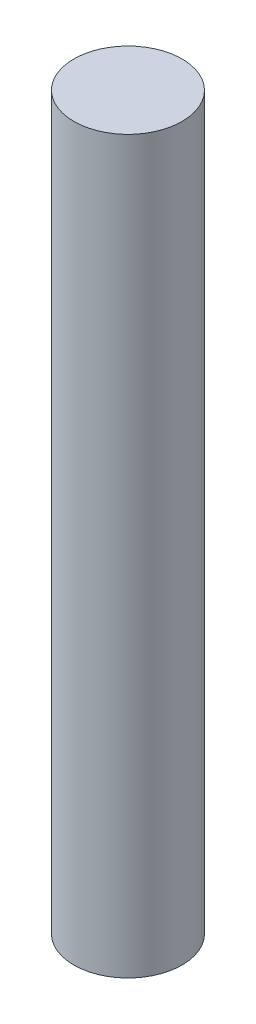
SolidWorks part; units mm, degrees
ref_plane "前视基准面" through (0, 0, 0) normal (0, 0, 1) x (1, 0, 0)
ref_plane "上视基准面" through (0, 0, 0) normal (0, 1, 0) x (1, 0, 0)
ref_plane "右视基准面" through (0, 0, 0) normal (1, 0, 0) x (0, 0, -1)
sketch "草图1" plane through (0, 0, 0) normal (0, 1, 0) x (1, 0, 0)
  circle A0 centre (0, 0) radius 1
extrude "凸台-拉伸1" add sketch "草图1" along normal blind 13.5
